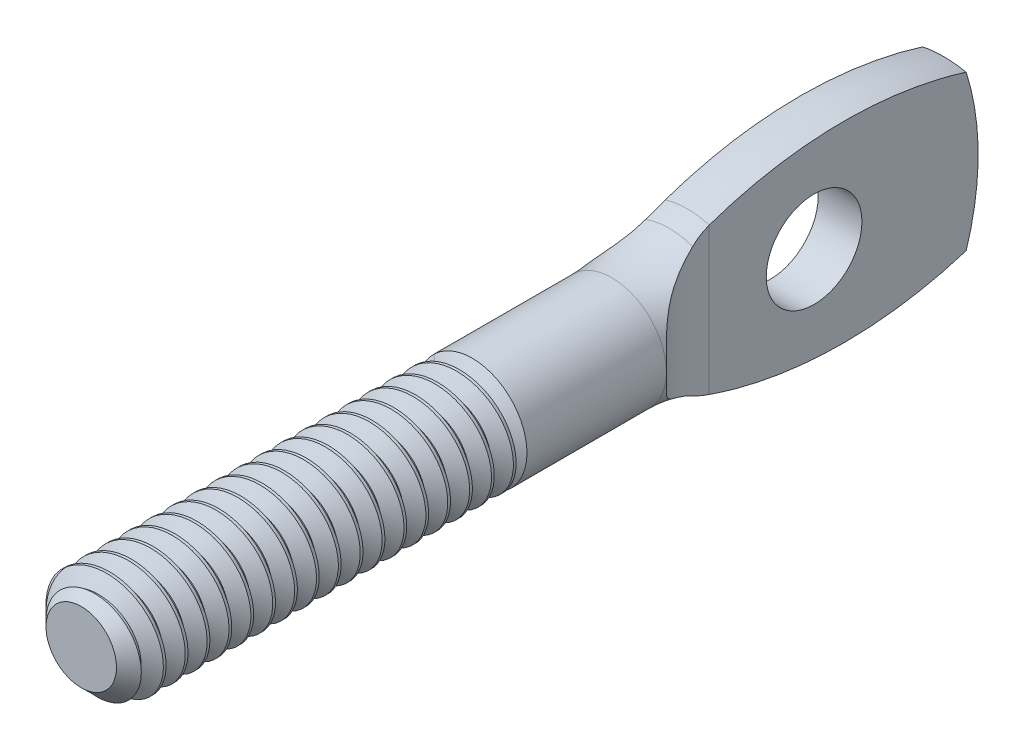
SolidWorks part; units mm, degrees
ref_plane "Front Plane" through (0, 0, 0) normal (0, 0, 1) x (1, 0, 0)
ref_plane "Top Plane" through (0, 0, 0) normal (0, 1, 0) x (1, 0, 0)
ref_plane "Right Plane" through (0, 0, 0) normal (1, 0, 0) x (0, 0, -1)
sketch "Sketch1" plane through (0, 0, 0) normal (0, 0, 1) x (1, 0, 0)
  circle A0 centre (0, 0) radius 3.175
  dimension "OD" = 6.35
extrude "Extrude1" add sketch "Sketch1" against normal blind 50.8
sketch "Sketch2" plane through (0, 0, 0) normal (0, 0, 1) x (1, 0, 0)
  circle A0 centre (0, 0) radius 3.175 construction
  circle A1 centre (0, 0) radius 3.175
curve "Helix/Spiral1" pitch 1.27 height 52.07 turns 41 parameters "pitch"=1.27
sketch "Sketch3" plane through (0, 0, 0) normal (1, 0, 0) x (0, 0, -1)
  line L0 (-1.1113, 3.175) -> (-0.635, 2.3501)
  line L1 (-0.635, 2.3501) -> (-0.4763, 2.3501)
  line L2 (-0.4763, 2.3501) -> (0, 3.175)
  line L3 (-1.1113, 3.175) -> (0, 3.175)
  line L4 (-0.5556, 3.175) -> (-0.5556, 2.3501) construction
  line L5 (-0.8731, 2.7626) -> (-0.2381, 2.7626) construction
  line L6 (0, 3.175) -> (0, -3.175) construction
  dimension "D1" = 0.1588
  dimension "D2" = 0.635
  dimension "D3" = 60
sweep "Cut-Sweep1" cut profiles "Sketch3" path "Helix/Spiral1"
sketch "Sketch4" plane through (0, 0, 0) normal (1, 0, 0) x (0, 0, -1)
  line L0 (1.1297, 3.175) -> (0, 2.0453)
  line L1 (0, 2.0453) -> (0, 3.175)
  line L2 (1.1297, 3.175) -> (0, 3.175)
  line L3 (-1.1113, 3.175) -> (0, 3.175) construction
  line L4 (0, 0) -> (7.0209, 0) construction
  dimension "D1" = 45
  dimension "D2" = 0.3048
revolve "Cut-Revolve1" cut sketch "Sketch4" angle 360 about L4
sketch "Sketch29" plane through (0, 0, 0) normal (1, 0, 0) x (0, 0, -1)
  line L0 (0, 0) -> (50.8, 0) construction
  line L1 (50.8, -2.3728) -> (50.8, 2.2654) construction
  line L2 (22.225, 0) -> (22.225, 2.3501)
  line L3 (22.225, 2.3501) -> (22.7013, 3.175)
  line L4 (50.8, 0) -> (50.8, 4.445)
  line L5 (22.7013, 3.175) -> (30.7975, 3.175)
  line L6 (50.8, 5.715) -> (22.225, 5.715) construction
  line L7 (50.8, 0) -> (22.225, 0)
  arc A0 (50.8, 4.445) -> (35.1875, 4.445) centre (42.9938, -18.9111) ccw
  arc A1 (30.7975, 3.175) -> (34.1313, 3.9953) centre (30.7975, 10.3597) ccw
  arc A2 (34.1313, 3.9953) -> (35.1875, 4.445) centre (37.465, -2.3692) cw
  point P19 (22.225, 3.175)
  dimension "D1" = 30
  dimension "thread length" = 22.225
  dimension "D3" = 5.715
  dimension "D4" = 1.27
  dimension "D5" = 28.575
  dimension "D2" = 16.6687
  dimension "D6" = 3.3337
revolve "Revolve2" add sketch "Sketch29" angle 360 about L0
sketch "Sketch30" plane through (0, 0, 0) normal (1, 0, 0) x (0, 0, -1)
  line L0 (50.8, 0) -> (22.225, 0) construction
  line L1 (52.324, 5.715) -> (49.657, 5.715)
  line L2 (52.324, 5.715) -> (52.324, -5.715)
  line L3 (52.324, -5.715) -> (49.657, -5.715)
  line L4 (50.8, 5.715) -> (22.225, 5.715) construction
  line L5 (50.8, 0) -> (50.8, 4.445) construction
  line L6 (50.8, 5.715) -> (41.275, 5.715) construction
  line L8 (41.275, 5.715) -> (31.75, 5.715) construction
  line L10 (31.75, 5.715) -> (22.225, 5.715) construction
  arc A0 (49.657, 5.715) -> (49.657, -5.715) centre (35.941, 0) cw
  circle A1 centre (41.275, 0) radius 2.7781
  dimension "hole" = 5.5562
  dimension "D1" = 1.143
  dimension "D2" = 1.524
extrude "Cut-Extrude7" cut sketch "Sketch30" against normal mid plane 25.4
sketch "Sketch31" plane through (0, 0, 0) normal (0, 1, 0) x (1, 0, 0)
  line L0 (1.27, 50.8) -> (1.27, 35.1875)
  line L1 (4.445, 50.8) -> (-4.445, 50.8) construction
  line L3 (3.175, 30.7975) -> (-3.175, 30.7975) construction
  line L4 (4.445, 35.1875) -> (-4.445, 35.1875) construction
  line L6 (0, 0) -> (0, 52.2383) construction
  line L7 (-3.175, 0) -> (3.175, 0) construction
  line L8 (-1.27, 50.8) -> (-1.27, 35.1875)
  line L9 (1.27, 50.8) -> (13.97, 50.8)
  line L10 (3.175, 30.7975) -> (13.97, 30.7975)
  line L11 (13.97, 30.7975) -> (13.97, 50.8)
  line L12 (-1.27, 50.8) -> (-13.97, 50.8)
  line L13 (-13.97, 50.8) -> (-13.97, 30.7975)
  line L14 (-3.175, 30.7975) -> (-13.97, 30.7975)
  arc A0 (1.27, 35.1875) -> (3.175, 30.7975) centre (7.2808, 35.1875) ccw
  arc A1 (-1.27, 35.1875) -> (-3.175, 30.7975) centre (-7.2808, 35.1875) cw
  dimension "D1" = 2.54
  dimension "D2" = 12.7
extrude "Cut-Extrude8" cut sketch "Sketch31" against normal mid plane 25.4
sketch "Sketch17" plane through (0, 0, 0) normal (1, 0, 0) x (0, 0, -1)
  line L0 (10.795, 3.175) -> (10.795, -3.175) construction
  line L1 (0, -3.175) -> (0, 3.175) construction
  dimension "D1" = 10.795
equation "\"D3@Helix/Spiral1\" = \"screw length@Extrude1\"+\"pitch@Helix/Spiral1\""
equation "\"D1@Sketch3\" = \"pitch@Helix/Spiral1\"*.125"
equation "\"D2@Sketch3\" = \"pitch@Helix/Spiral1\"*.5"
equation "\"D1@Sketch17\" = \"pitch@Helix/Spiral1\"*8.5"
equation "\"D3@Sketch29\" = \"OD@Sketch1\"*1.8/2"
equation "\"D1@Sketch31\" = \"OD@Sketch1\"*.4"
equation "\"D2@Sketch29\" = \"hole@Sketch30\" * 3"
equation "\"D6@Sketch29\" = \"D2@Sketch29\" * .2"
equation "\"D1@Sketch30\" = \"D3@Sketch29\" * .2"
